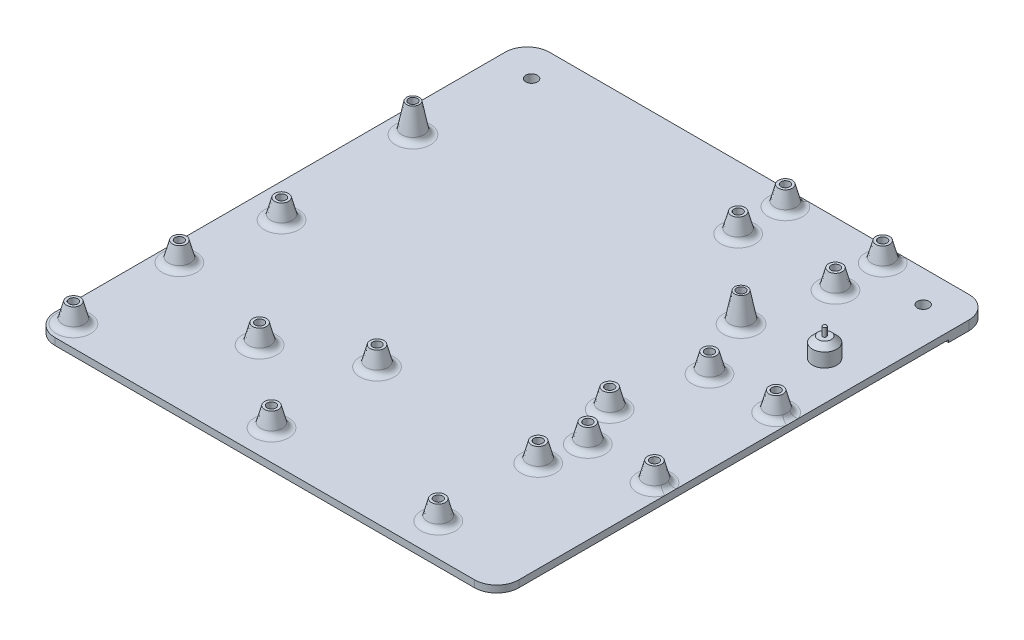
SolidWorks part; units mm, degrees
ref_plane "Front Plane" through (0, 0, 0) normal (0, 0, 1) x (1, 0, 0)
ref_plane "Top Plane" through (0, 0, 0) normal (0, 1, 0) x (1, 0, 0)
ref_plane "Right Plane" through (0, 0, 0) normal (1, 0, 0) x (0, 0, -1)
sketch "Backplane" plane through (0, 0, 0) normal (0, 1, 0) x (1, 0, 0)
  line L0 (-80.645, 87.63) -> (8.255, 87.63)
  line L1 (-106.045, -113.03) -> (106.045, -113.03)
  line L2 (-106.045, -113.03) -> (-106.045, 113.03)
  line L3 (-106.045, 113.03) -> (106.045, 113.03)
  line L4 (106.045, -113.03) -> (106.045, 113.03)
  line L5 (-106.045, -113.03) -> (106.045, 113.03) construction
  line L6 (-106.045, 113.03) -> (106.045, -113.03) construction
  line L7 (-106.045, 113.03) -> (-80.645, 113.03) construction
  line L8 (-106.045, 113.03) -> (-106.045, 87.63) construction
  line L9 (-106.045, 87.63) -> (-80.645, 87.63)
  line L10 (-80.645, 113.03) -> (-80.645, 87.63)
  line L11 (106.045, 113.03) -> (80.645, 113.03) construction
  line L12 (106.045, 113.03) -> (106.045, 87.63) construction
  line L13 (106.045, 87.63) -> (80.645, 87.63)
  line L14 (80.645, 113.03) -> (80.645, 87.63)
  line L15 (8.255, 87.63) -> (8.255, 113.03)
  line L16 (0, 0) -> (0, 113.03) construction
  line L17 (-86.8807, 98.4941) -> (86.8807, 98.4941)
  line L18 (-86.8807, 98.4941) -> (-89.5477, 98.4941)
  circle A0 centre (-89.5477, 98.4941) radius 2.667
  circle A1 centre (89.5477, 98.4941) radius 2.667
  point P0 (0, 0)
  point P19 (0, 98.4941)
  dimension "D5" = 5.334
  dimension "D1" = 212.09
  dimension "D2" = 226.06
  dimension "D3" = 173.7614
  dimension "D4" = 2.667
sketch "Protoboard1" plane through (0, 0, 0) normal (0, 1, 0) x (1, 0, 0)
  line L0 (59.2817, 74.5827) -> (59.2817, 49.1827) construction
  line L1 (-98.1983, 23.7827) -> (59.2817, 23.7827)
  line L2 (-98.1983, 23.7827) -> (-98.1983, 74.5827)
  line L3 (-98.1983, 74.5827) -> (59.2817, 74.5827)
  line L4 (59.2817, 23.7827) -> (59.2817, 74.5827)
  line L5 (-98.1983, 23.7827) -> (59.2817, 74.5827) construction
  line L6 (-98.1983, 74.5827) -> (59.2817, 23.7827) construction
  line L7 (-92.8897, 49.1827) -> (53.9731, 49.1827)
  line L8 (-19.4583, 49.1827) -> (-19.4583, 23.7827) construction
  line L9 (-92.8897, 49.1827) -> (-94.4772, 49.1827)
  circle A4 centre (-94.4772, 49.1827) radius 1.5875
  circle A5 centre (-94.4772, 49.1827) radius 5.5499
  circle A6 centre (55.5606, 49.1827) radius 1.5875
  circle A7 centre (55.5606, 49.1827) radius 5.5499
  circle A8 centre (-94.4772, 49.1827) radius 1.9939
  circle A9 centre (55.5606, 49.1827) radius 1.9939
  point P0 (-19.4583, 49.1827)
  point P9 (-19.4583, 49.1827)
  point P10 (-19.4583, 49.1827)
  dimension "D5" = 3.175
  dimension "D6" = 11.0998
  dimension "D7" = 3.9878
  dimension "D3" = 157.48
  dimension "D1" = 73.4314
  dimension "D2" = 1.5875
sketch "Protoboard2" plane through (0, 0, 0) normal (0, 1, 0) x (1, 0, 0)
  line L0 (62.992, 10.795) -> (62.992, -14.605) construction
  line L1 (-94.488, -40.005) -> (62.992, -40.005)
  line L2 (-94.488, -40.005) -> (-94.488, 10.795)
  line L3 (-94.488, 10.795) -> (62.992, 10.795)
  line L4 (62.992, -40.005) -> (62.992, 10.795)
  line L5 (-94.488, -40.005) -> (62.992, 10.795) construction
  line L6 (-94.488, 10.795) -> (62.992, -40.005) construction
  line L7 (-89.1794, -14.605) -> (57.6834, -14.605)
  line L8 (-15.748, -14.605) -> (-15.748, -40.005) construction
  line L9 (-89.1794, -14.605) -> (-90.7669, -14.605)
  circle A0 centre (-90.7669, -14.605) radius 1.5875
  circle A1 centre (-90.7669, -14.605) radius 5.5499
  circle A4 centre (-90.7669, -14.605) radius 1.9939
  circle A6 centre (59.2709, -14.605) radius 1.5875
  circle A7 centre (59.2709, -14.605) radius 1.9939
  circle A8 centre (59.2709, -14.605) radius 5.5499
  point P0 (-15.748, -14.605)
  point P9 (-15.748, -14.605)
  point P10 (-15.748, -14.605)
  dimension "D5" = 3.175
  dimension "D6" = 11.0998
  dimension "D7" = 3.9878
  dimension "D4" = 1.5875
  dimension "D1" = 157.48
  dimension "D3" = 73.4314
sketch "ADS1256" plane through (0, 0, 0) normal (0, 1, 0) x (1, 0, 0)
  line L0 (83.3697, -5.6387) -> (83.3697, 21.3806)
  line L1 (65.6786, -35.7758) -> (101.0608, -35.7758)
  line L2 (65.6786, -35.7758) -> (65.6786, 24.4984)
  line L3 (65.6786, 24.4984) -> (101.0608, 24.4984)
  line L4 (101.0608, -35.7758) -> (101.0608, 24.4984)
  line L5 (65.6786, -35.7758) -> (101.0608, 24.4984) construction
  line L6 (65.6786, 24.4984) -> (101.0608, -35.7758) construction
  line L7 (83.3697, 21.3806) -> (83.3697, 22.1743)
  line L8 (83.3697, 22.1743) -> (97.8159, 22.1743)
  line L9 (97.8159, 22.1743) -> (98.6097, 22.1743)
  line L10 (83.3697, -5.6387) -> (89.9657, -5.6387) construction
  circle A0 centre (98.6097, 22.1743) radius 1.5875
  circle A1 centre (98.6097, 22.1743) radius 5.5499
  circle A8 centre (98.6097, 22.1743) radius 1.9939
  circle A12 centre (68.1297, 22.1743) radius 1.5875
  circle A13 centre (68.1297, 22.1743) radius 1.9939
  circle A14 centre (68.1297, 22.1743) radius 5.5499
  circle A15 centre (98.6097, -33.4517) radius 1.5875
  circle A16 centre (98.6097, -33.4517) radius 1.9939
  circle A17 centre (98.6097, -33.4517) radius 5.5499
  circle A18 centre (68.1297, -33.4517) radius 1.5875
  circle A19 centre (68.1297, -33.4517) radius 1.9939
  circle A20 centre (68.1297, -33.4517) radius 5.5499
  point P0 (83.3697, -5.6387)
  dimension "D3" = 3.175
  dimension "D4" = 11.0998
  dimension "D5" = 3.9878
  dimension "D1" = 0.7937
  dimension "D2" = 0.7937
sketch "3V_Buck" plane through (0, 0, 0) normal (0, 1, 0) x (1, 0, 0)
  circle A0 centre (88.2115, 54.7666) radius 1.5875
  circle A1 centre (88.2115, 54.7666) radius 5.5499
  circle A2 centre (88.2115, 54.7666) radius 1.9939
  circle A3 centre (88.2115, 54.7666) radius 0.8636
  dimension "D1" = 3.175
  dimension "D2" = 11.0998
  dimension "D3" = 3.9878
sketch "Relay" plane through (0, 0, 0) normal (0, 1, 0) x (1, 0, 0)
  line L1 (16.3302, 81.8626) -> (66.6036, 81.8626)
  line L2 (16.3302, 81.8626) -> (16.3302, 108.1272)
  line L3 (16.3302, 108.1272) -> (66.6036, 108.1272)
  line L4 (66.6036, 81.8626) -> (66.6036, 108.1272)
  line L5 (16.3302, 81.8626) -> (66.6036, 108.1272) construction
  line L6 (16.3302, 108.1272) -> (66.6036, 81.8626) construction
  line L7 (41.4669, 94.9949) -> (41.4669, 104.7104)
  line L8 (41.4669, 104.7104) -> (41.4669, 105.7899)
  line L9 (41.4669, 105.7899) -> (62.1298, 105.7899)
  line L10 (62.1298, 105.7899) -> (63.7173, 105.7899)
  line L11 (41.4669, 94.9949) -> (31.7125, 94.9949) construction
  circle A0 centre (63.7173, 105.7899) radius 1.5875
  circle A1 centre (63.7173, 105.7899) radius 5.5499
  circle A8 centre (63.7173, 105.7899) radius 1.9939
  circle A12 centre (19.2165, 105.7899) radius 1.5875
  circle A13 centre (19.2165, 105.7899) radius 1.9939
  circle A14 centre (19.2165, 105.7899) radius 5.5499
  circle A15 centre (63.7173, 84.1999) radius 1.5875
  circle A16 centre (63.7173, 84.1999) radius 1.9939
  circle A17 centre (63.7173, 84.1999) radius 5.5499
  circle A18 centre (19.2165, 84.1999) radius 1.5875
  circle A19 centre (19.2165, 84.1999) radius 1.9939
  circle A20 centre (19.2165, 84.1999) radius 5.5499
  dimension "D4" = 3.175
  dimension "D5" = 11.0998
  dimension "D6" = 3.9878
  dimension "D1" = 1.0795
  dimension "D2" = 20.6629
  dimension "D3" = 1.5875
sketch "ServoBoard" plane through (0, 0, 0) normal (0, 1, 0) x (1, 0, 0)
  line L0 (-97.2211, -103.339) -> (-97.2211, -58.0508)
  line L1 (-111.1276, -105.5869) -> (-42.2428, -105.5869)
  line L2 (-111.1276, -105.5869) -> (-111.1276, -52.1961)
  line L3 (-111.1276, -52.1961) -> (-42.2428, -52.1961)
  line L4 (-42.2428, -105.5869) -> (-42.2428, -52.1961)
  line L5 (-111.1276, -105.5869) -> (-42.2428, -52.1961) construction
  line L6 (-111.1276, -52.1961) -> (-42.2428, -105.5869) construction
  line L7 (-111.1276, -105.5869) -> (-98.8086, -105.5869)
  line L8 (-111.1276, -105.5869) -> (-111.1276, -104.9265)
  line L9 (-111.1276, -104.9265) -> (-98.8086, -104.9265)
  line L10 (-98.8086, -105.5869) -> (-98.8086, -104.9265)
  line L11 (-98.8086, -104.9265) -> (-97.2211, -104.9265)
  line L12 (-98.8086, -104.9265) -> (-98.8086, -103.339)
  line L13 (-98.8086, -103.339) -> (-97.2211, -103.339)
  line L14 (-97.2211, -104.9265) -> (-97.2211, -103.339)
  line L15 (-97.2211, -58.0508) -> (-97.2211, -54.8758)
  line L16 (-97.2211, -103.339) -> (-46.2337, -69.1904)
  line L17 (-97.2211, -54.8758) -> (-46.2334, -69.1905)
  circle A0 centre (-97.2211, -103.339) radius 1.651
  circle A1 centre (-97.2211, -103.339) radius 1.9939
  circle A2 centre (-97.2211, -103.339) radius 5.5499
  circle A3 centre (-97.2211, -54.8758) radius 1.5875
  circle A4 centre (-97.2211, -54.8758) radius 1.9939
  circle A5 centre (-97.2211, -54.8758) radius 5.5499
  circle A6 centre (-46.2334, -69.1905) radius 1.5875
  circle A7 centre (-46.2337, -69.1904) radius 1.9939
  circle A8 centre (-46.2337, -69.1904) radius 5.5499
  point P0 (-76.6852, -78.8915)
  dimension "D3" = 1.5875
  dimension "D8" = 3.9878
  dimension "D9" = 11.0998
  dimension "D11" = 3.175
  dimension "D12" = 3.9878
  dimension "D13" = 11.0998
  dimension "D7" = 3.302
  dimension "D17" = 3.175
  dimension "D18" = 3.9878
  dimension "D19" = 11.0998
  dimension "D1" = 68.8848
  dimension "D2" = 53.3908
  dimension "D4" = 1.5875
  dimension "D5" = 12.319
  dimension "D6" = 0.6604
  dimension "D10" = 3.175
  dimension "D14" = 45.2882
  dimension "D15" = 74.318
  dimension "D16" = 56.188
sketch "Nucleo" plane through (0, 0, 0) normal (0, 1, 0) x (1, 0, 0)
  line L0 (64.3218, -98.0391) -> (64.3218, -52.3191)
  line L1 (-39.9579, -110.32) -> (93.3921, -110.32)
  line L2 (-39.9579, -110.32) -> (-39.9579, -40.6732)
  line L3 (-39.9579, -40.6732) -> (93.3921, -40.6732)
  line L4 (93.3921, -110.32) -> (93.3921, -40.6732)
  line L5 (-39.9579, -110.32) -> (93.3921, -40.6732) construction
  line L6 (-39.9579, -40.6732) -> (93.3921, -110.32) construction
  line L11 (93.3921, -110.32) -> (65.9093, -110.32)
  line L12 (93.3921, -110.32) -> (93.3921, -99.6266)
  line L13 (93.3921, -99.6266) -> (65.9093, -99.6266)
  line L14 (65.9093, -110.32) -> (65.9093, -99.6266)
  line L15 (65.9093, -99.6266) -> (64.3218, -99.6266)
  line L16 (65.9093, -99.6266) -> (65.9093, -98.0391)
  line L17 (65.9093, -98.0391) -> (64.3218, -98.0391)
  line L18 (64.3218, -99.6266) -> (64.3218, -98.0391)
  line L19 (64.3218, -75.1791) -> (-10.6682, -75.1791)
  line L21 (-10.6682, -51.0491) -> (-10.6682, -99.3091)
  circle A0 centre (64.3218, -98.0391) radius 1.5875
  circle A1 centre (64.3218, -98.0391) radius 1.9939
  circle A2 centre (64.3218, -98.0391) radius 5.5499
  circle A3 centre (64.3218, -52.3191) radius 1.5875
  circle A4 centre (64.3218, -52.3191) radius 1.9939
  circle A5 centre (64.3218, -52.3191) radius 5.5499
  circle A6 centre (-10.6682, -99.3091) radius 1.5875
  circle A7 centre (-10.6682, -99.3091) radius 1.9939
  circle A8 centre (-10.6682, -99.3091) radius 5.5499
  circle A12 centre (-10.6682, -51.0491) radius 1.5875
  circle A13 centre (-10.6682, -51.0491) radius 1.9939
  circle A14 centre (-10.6682, -51.0491) radius 5.5499
  point P0 (26.7171, -75.4966)
  point P32 (-10.6682, -75.1791)
  dimension "D2" = 1.5875
  dimension "D7" = 3.175
  dimension "D8" = 3.9878
  dimension "D9" = 11.0998
  dimension "D11" = 3.175
  dimension "D12" = 3.9878
  dimension "D13" = 11.0998
  dimension "D16" = 3.175
  dimension "D17" = 3.9878
  dimension "D18" = 11.0998
  dimension "D3" = 133.35
  dimension "D4" = 69.6468
  dimension "D1" = 1.5875
  dimension "D5" = 27.4828
  dimension "D6" = 10.6934
  dimension "D10" = 45.72
  dimension "D23" = 74.99
  dimension "D24" = 48.26
extrude "Backplane_Extrude" add sketch "Backplane" against normal blind 4.318 contours L17 L15 L0 L9 L2 L1 L4 L13 L14 | L17 L10 L0 L15 | L10 L17 L15 L3 | L15 L17 L14 L3 | A1 L14 L13 L4 L3 | A0 L10 L3 L2 L9 region at (-36.195, 0, -93.062) region at (0.8065, 0, 10.781) region at (-93.4812, 0, -100.3959) region at (-36.195, 0, -105.762) region at (44.45, 0, -105.762) region at (93.4812, 0, -100.3959)
fillet "Backplane_Fillets" radius 10.16 4 edges at (106.045, -2.159, 113.03) (-106.045, -2.159, 113.03) (106.045, -2.159, -113.03) (-106.045, -2.159, -113.03)
extrude "Boss-Extrude2" add sketch "Protoboard1" along normal blind 13.335 contours A8 A5 L2 | L2 A5 | A9 A7 L4 | A7 L4 region at (-98.9412, 0, -49.1827) region at (-98.0536, 0, -49.1827) region at (53.3666, 0, -44.2427) region at (60.0247, 0, -49.1827)
draft "Draft1" type of draft neutral plane draft angle 11.25 faces to draft 2 face at (55.5606, 13.335, -43.6328) face at (-94.4772, 13.335, -43.6328) neutral plane through (0, 0, 0) neutral plane normal (0, 1, 0) parameters "D1"=11.25
fillet "Fillet5" radius 3.048 2 edges at (55.5606, 0, -43.6328) (-94.4772, 0, -43.6328)
extrude "Boss-Extrude3" add sketch "Protoboard2" along normal blind 8.89 contours A4 A1 L2 | L2 A1 | A8 A7 L4 | A8 L4 region at (-95.2309, 0, 14.605) region at (-94.3434, 0, 14.605) region at (57.0769, 0, 19.545) region at (63.7349, 0, 14.605)
draft "Draft2" type of draft neutral plane draft angle 15 faces to draft 2 face at (59.2709, 8.89, 20.1549) face at (-90.7669, 8.89, 20.1549) neutral plane through (0, 0, 0) neutral plane normal (0, 1, 0) parameters "D1"=15
fillet "Fillet6" radius 3.048 2 edges at (59.2709, 0, 20.1549) (-90.7669, 0, 20.1549)
extrude "Boss-Extrude4" add sketch "ADS1256" along normal blind 8.89 contours L3 L2 | L2 L3 | L4 A1 L3 | A8 A1 L4 L3 | L4 L1 | L1 L4 | L1 L2 | L2 L1 region at (69.706, 0, 31.7947) region at (69.4241, 0, 35.9251) region at (97.0334, 0, 31.7947) region at (97.3153, 0, 35.9251) region at (64.3596, 0, -26.0412) region at (69.706, 0, -20.5173) region at (97.0334, 0, -20.5173) region at (101.2101, 0, -20.8467)
draft "Draft3" type of draft neutral plane draft angle 15 faces to draft 4 face at (68.1297, 8.89, 39.0016) face at (98.6097, 8.89, 39.0016) face at (68.1297, 8.89, -16.6244) face at (98.6097, 8.89, -16.6244) neutral plane through (0, 0, 0) neutral plane normal (0, 1, 0) parameters "D1"=15
fillet "Fillet7" radius 3.048 4 edges at (98.6097, 0, -16.6244) (98.6097, 0, 39.0016) (68.1297, 0, 39.0016) (68.1297, 0, -16.6244)
extrude "Boss-Extrude5" add sketch "3V_Buck" along normal blind 8.89 contours A1 A2 | A2 A0 | A0 A3 | A3 region at (86.6689, 0, -54.7666) region at (82.8185, 0, -54.7666) region at (86.274, 0, -54.7666) region at (88.2115, 0, -54.7666)
sketch "Sketch4" plane through (0, 8.89, 0) normal (0, 1, 0) x (1, 0, 0)
  circle A0 centre (85.177, 50.1306) radius 0.0092
  circle A1 centre (88.2115, 54.7666) radius 0.8636
extrude "Boss-Extrude9" add sketch "Sketch4" along normal blind 3.81
chamfer "Chamfer1" distance 2.54 angle 45 1 edges at (88.2115, 8.89, -49.2167)
extrude "Boss-Extrude6" add sketch "Relay" along normal blind 8.89 contours A13 L2 L3 | A8 A1 L4 L3 | L4 A1 L3 | L4 L1 | L1 L4 A20 | L1 A15 L2 A19 | L2 A15 L1 | A14 L3 L2 A13 region at (20.5049, 0, -85.8218) region at (20.2902, 0, -81.715) region at (62.429, 0, -85.8218) region at (62.6436, 0, -81.715) region at (15.6168, 0, -109.8181) region at (20.5049, 0, -104.168) region at (62.429, 0, -104.168) region at (66.7513, 0, -104.5884)
draft "Draft5" type of draft neutral plane draft angle 15 faces to draft 4 face at (19.2165, 8.89, -78.65) face at (63.7173, 8.89, -78.65) face at (63.7173, 8.89, -100.24) face at (19.2165, 8.89, -100.24) neutral plane through (0, 0, 0) neutral plane normal (0, 1, 0) parameters "D1"=15
fillet "Fillet9" radius 3.048 4 edges at (63.7173, 0, -100.24) (19.2165, 0, -78.65) (63.7173, 0, -78.65) (19.2165, 0, -100.24)
extrude "Boss-Extrude7" add sketch "ServoBoard" along normal blind 8.89 contours L0 A5 L17 A4 L15 | L17 A5 L3 L0 L15 A4 | L3 A5 | L4 A8 | L4 A8 L17 A7 L16 | L17 A8 L16 A7 | L1 A2 L16 A1 L11 L10 | L7 A2 L1 | L0 A2 L9 L12 A1 | L16 A2 L0 A1 | L9 A2 L7 L10 region at (-100.0287, 0, 101.4937) region at (-95.3888, 0, 99.9065) region at (-93.8385, 0, 103.5104) region at (-101.8809, 0, 57.6277) region at (-94.9419, 0, 57.8828) region at (-100.6175, 0, 105.253) region at (-50.1111, 0, 69.809) region at (-49.2869, 0, 71.4099) region at (-97.2211, 0, 51.018) region at (-97.2211, 0, 106.9485) region at (-41.611, 0, 69.1904)
draft "Draft6" type of draft neutral plane draft angle 15 faces to draft 3 face at (-97.2211, 8.89, 60.4257) face at (-46.2337, 8.89, 74.7403) face at (-97.2211, 8.89, 108.8889) neutral plane through (0, 0, 0) neutral plane normal (0, 1, 0) parameters "D1"=15
fillet "Fillet10" radius 3.048 3 edges at (-97.2211, 0, 108.8889) (-46.2337, 0, 74.7403) (-97.2211, 0, 60.4257)
extrude "Boss-Extrude8" add sketch "Nucleo" along normal blind 8.89 contours A8 A7 | A14 A13 | A5 A4 | L0 A2 L14 L15 A1 | L13 A2 L0 A1 L16 | L14 A2 L13 region at (62.1542, 0, 98.4809) region at (67.1295, 0, 96.1938) region at (-6.8548, 0, 95.4957) region at (-14.4816, 0, 47.2357) region at (60.5084, 0, 48.5057) region at (67.3593, 0, 101.0766)
draft "Draft7" type of draft neutral plane draft angle 15 faces to draft 4 face at (64.3218, 8.89, 57.869) face at (-10.6682, 8.89, 56.599) face at (-10.6682, 8.89, 104.859) face at (64.3218, 8.89, 103.589) neutral plane through (0, 0, 0) neutral plane normal (0, 1, 0) parameters "D1"=15
fillet "Fillet11" radius 3.048 4 edges at (64.3218, 0, 103.589) (64.3218, 0, 57.869) (-10.6682, 0, 104.859) (-10.6682, 0, 56.599)
sketch "Sketch1" plane through (0, -4.318, 0) normal (0, -1, 0) x (1, 0, 0)
  line L1 (122.4055, -93.577) -> (-137.5135, -93.577)
  line L2 (122.4055, -93.577) -> (122.4055, 121.018)
  line L3 (122.4055, 121.018) -> (-137.5135, 121.018)
  line L4 (-137.5135, -93.577) -> (-137.5135, 121.018)
extrude "Cut-Extrude1" cut sketch "Sketch1" against normal blind 1.143
equation "\"D4@Backplane\"=.210/2"
equation "\"D2@Relay\"=1.627/2"
equation "\"D1@Protoboard1\" = 5.782 / 2"
equation "\"M3_PCB_Hole_Diam\"= 0.125in"
equation "\"M3_Insert_OuterFeature_Diam\"= \"M3_Print_CAD_Hole_Diam\" + ( 0.14 * 2 )"
equation "\"D2@Protoboard1\" = \"M3_PCB_Hole_Diam\" / 2"
equation "\"D5@Protoboard1\" = \"M3_PCB_Hole_Diam\""
equation "\"D6@Protoboard1\" = \"M3_Insert_OuterFeature_Diam\""
equation "\"D1@Relay\"=(\"M3_PCB_Hole_Diam\"/2)-0.02"
equation "\"D3@Relay\"=\"M3_PCB_Hole_Diam\"/2"
equation "\"D4@Relay\"=\"M3_PCB_Hole_Diam\""
equation "\"D5@Relay\"=\"M3_Insert_OuterFeature_Diam\""
equation "\"D1@ADS1256\"=(\"M3_PCB_Hole_Diam\"/2)-(0.25*\"M3_PCB_Hole_Diam\")"
equation "\"D2@ADS1256\"=(\"M3_PCB_Hole_Diam\"/2)-(0.25*\"M3_PCB_Hole_Diam\")"
equation "\"D3@ADS1256\"=\"M3_PCB_Hole_Diam\""
equation "\"D4@ADS1256\"=\"M3_Insert_OuterFeature_Diam\""
equation "\"M3_Print_CAD_Hole_Diam\"= 0.157in"
equation "\"D5@ADS1256\"=\"M3_Print_CAD_Hole_Diam\""
equation "\"D7@Protoboard1\" = \"M3_Print_CAD_Hole_Diam\""
equation "\"D6@Relay\"=\"M3_Print_CAD_Hole_Diam\""
equation "\"D3@3V_Buck\"=\"M3_Print_CAD_Hole_Diam\""
equation "\"D1@3V_Buck\"=\"M3_PCB_Hole_Diam\""
equation "\"D1@Nucleo\"=\"M3_PCB_Hole_Diam\"/2"
equation "\"D2@Nucleo\"=\"M3_PCB_Hole_Diam\"/2"
equation "\"D7@Nucleo\"=\"M3_PCB_Hole_Diam\""
equation "\"D8@Nucleo\"=\"M3_Print_CAD_Hole_Diam\""
equation "\"D9@Nucleo\"=\"M3_Insert_OuterFeature_Diam\""
equation "\"D11@Nucleo\"=\"M3_PCB_Hole_Diam\""
equation "\"D12@Nucleo\"=\"M3_Print_CAD_Hole_Diam\""
equation "\"D13@Nucleo\"=\"M3_Insert_OuterFeature_Diam\""
equation "\"D16@Nucleo\"=\"M3_PCB_Hole_Diam\""
equation "\"D17@Nucleo\"=\"M3_Print_CAD_Hole_Diam\""
equation "\"D18@Nucleo\"=\"M3_Insert_OuterFeature_Diam\""
equation "\"D3@ServoBoard\"=\"M3_PCB_Hole_Diam\"/2"
equation "\"D4@ServoBoard\"=\"M3_PCB_Hole_Diam\"/2"
equation "\"D8@ServoBoard\"=\"M3_Print_CAD_Hole_Diam\""
equation "\"D9@ServoBoard\"=\"M3_Insert_OuterFeature_Diam\""
equation "\"D10@ServoBoard\"=\"M3_PCB_Hole_Diam\""
equation "\"D11@ServoBoard\"=\"M3_PCB_Hole_Diam\""
equation "\"D12@ServoBoard\"=\"M3_Print_CAD_Hole_Diam\""
equation "\"D13@ServoBoard\"=\"M3_Insert_OuterFeature_Diam\""
equation "\"D17@ServoBoard\"=\"M3_PCB_Hole_Diam\""
equation "\"D18@ServoBoard\"=\"M3_Print_CAD_Hole_Diam\""
equation "\"D19@ServoBoard\"=\"M3_Insert_OuterFeature_Diam\""
equation "\"M3_Insert_OuterFeature_DraftAngle\"= 15deg"
equation "\"D1@Draft1\"=\"M3_Insert_OuterFeature_DraftAngle\"*.75"
equation "\"M3_Insert_OuterFeature_FilletRad\"= 0.12in"
equation "\"D1@Fillet5\"=\"M3_Insert_OuterFeature_FilletRad\""
equation "\"M3_Insert_OuterFeature_ExtrudeHt\"= 0.35in"
equation "\"D1@Boss-Extrude2\"=\"M3_Insert_OuterFeature_ExtrudeHt\"*1.5"
equation "\"D6@Protoboard2\"=\"M3_Insert_OuterFeature_Diam\""
equation "\"D5@Protoboard2\"=\"M3_PCB_Hole_Diam\""
equation "\"D7@Protoboard2\"=\"M3_Print_CAD_Hole_Diam\""
equation "\"D1@Boss-Extrude3\"=\"M3_Insert_OuterFeature_ExtrudeHt\""
equation "\"D1@Draft2\"=\"M3_Insert_OuterFeature_DraftAngle\""
equation "\"D1@Fillet6\"=\"M3_Insert_OuterFeature_FilletRad\""
equation "\"D1@Boss-Extrude4\"=\"M3_Insert_OuterFeature_ExtrudeHt\""
equation "\"D1@Draft3\"=\"M3_Insert_OuterFeature_DraftAngle\""
equation "\"D1@Fillet7\"=\"M3_Insert_OuterFeature_FilletRad\""
equation "\"D1@Boss-Extrude5\"=\"M3_Insert_OuterFeature_ExtrudeHt\""
equation "\"D2@3V_Buck\"=\"M3_Insert_OuterFeature_Diam\""
equation "\"D1@Boss-Extrude6\"=\"M3_Insert_OuterFeature_ExtrudeHt\""
equation "\"D1@Draft5\"=\"M3_Insert_OuterFeature_DraftAngle\""
equation "\"D1@Boss-Extrude7\"=\"M3_Insert_OuterFeature_ExtrudeHt\""
equation "\"D1@Draft6\"=\"M3_Insert_OuterFeature_DraftAngle\""
equation "\"D1@Fillet10\"=\"M3_Insert_OuterFeature_FilletRad\""
equation "\"D1@Boss-Extrude8\"=\"M3_Insert_OuterFeature_ExtrudeHt\""
equation "\"D1@Draft7\"=\"M3_Insert_OuterFeature_DraftAngle\""
equation "\"D10@Nucleo\"=45.72mm"
equation "\"D23@Nucleo\"=133.4mm-12.7mm-16.51mm-3.8mm-2.54mm-22.86mm"
equation "\"D24@Nucleo\"=48.26mm"
equation "\"D1@Fillet11\"=\"M3_Insert_OuterFeature_FilletRad\""
equation "\"D1@Fillet9\"=\"M3_Insert_OuterFeature_FilletRad\""
